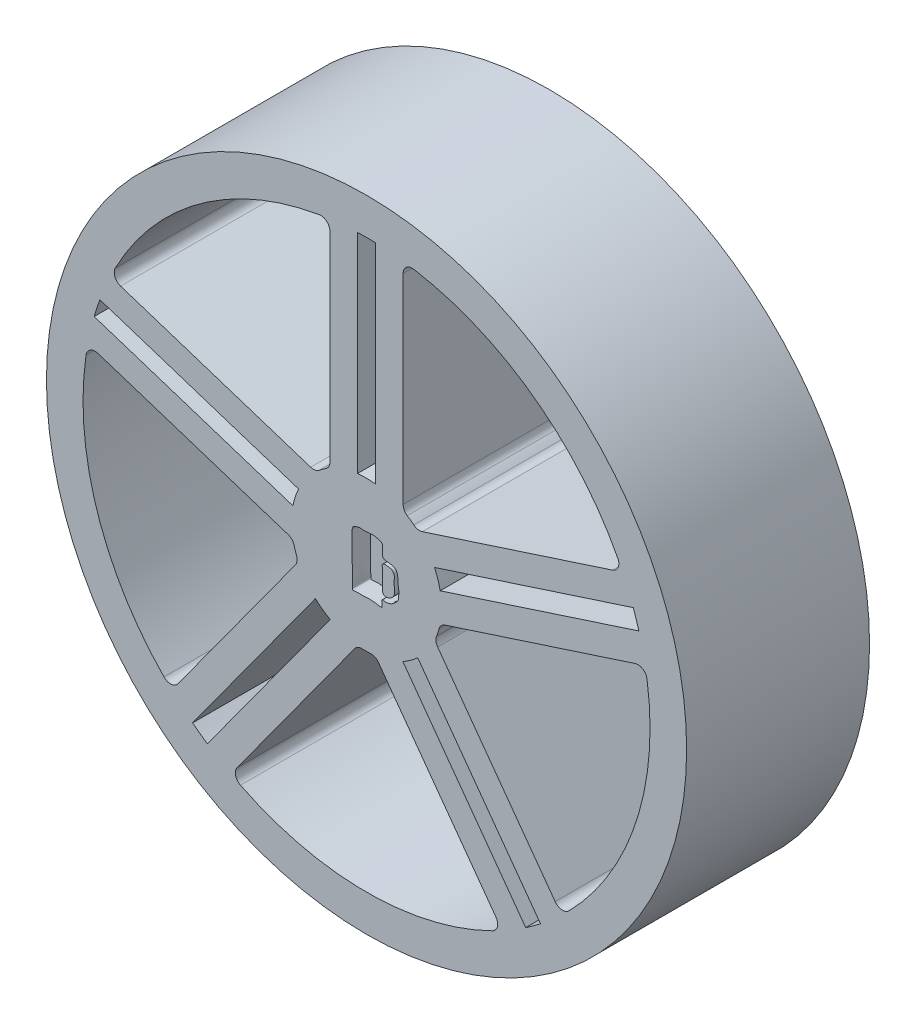
SolidWorks part; units mm, degrees
ref_plane "Plan de face" through (0, 0, 0) normal (0, 0, 1) x (1, 0, 0)
ref_plane "Plan de dessus" through (0, 0, 0) normal (0, 1, 0) x (1, 0, 0)
ref_plane "Plan de droite" through (0, 0, 0) normal (1, 0, 0) x (0, 0, -1)
sketch "Esquisse1" plane through (0, 0, 0) normal (0, 0, 1) x (1, 0, 0)
  circle A1 centre (0, 0) radius 2.1
  circle A2 centre (0, 0) radius 4.1
  dimension "D1" = 4.2
  dimension "D2" = 8.2
  dimension "D3" = 2
extrude "Boss.-Extru.1" add sketch "Esquisse1" along normal blind 6
sketch "Esquisse2" plane through (0, 0, 6) normal (0, 0, 1) x (1, 0, 0)
  line L0 (0, 0) -> (0, 4.1)
  line L1 (0, 4.1) -> (0, 3.4754)
  line L2 (0, 3.4754) -> (2, 3.4754)
  line L3 (2, 3.4754) -> (0, 3.4754)
  line L4 (0, 3.4754) -> (-2, 3.4754)
  line L6 (-2, 3.4754) -> (2, 3.4754)
  line L7 (-2, 3.4754) -> (-2, 16)
  line L8 (-2, 16) -> (2, 16)
  line L9 (2, 3.4754) -> (2, 16)
  line L10 (0, 3.4754) -> (0.5, 3.4754)
  line L11 (0, 3.4754) -> (0, 16)
  line L12 (0, 16) -> (0.5, 16)
  line L13 (0.5, 3.4754) -> (0.5, 16)
  line L14 (0, 16) -> (-0.5, 16)
  line L15 (0, 16) -> (0, 3.4754)
  line L16 (0, 3.4754) -> (-0.5, 3.4754)
  line L17 (-0.5, 16) -> (-0.5, 3.4754)
  circle A0 centre (0, 0) radius 4.1
  circle A1 centre (0, 0) radius 17.5
  circle A2 centre (0, 0) radius 15.5
  spline S0 degree 1 poles (-2, 4.9542) (-2, 16) knots 0 0 1 1
  dimension "D5" = 35
  dimension "D6" = 2
  dimension "D1" = 2
  dimension "D2" = 2
  dimension "D3" = 4
  dimension "D4" = 16
  dimension "D7" = 0.5
  dimension "D8" = 0.5
extrude "Boss.-Extru.3" add sketch "Esquisse2" along normal blind 10
fillet "Congé5" radius 0.5 4 edges at (2, 15.3704, 11) (-2, 15.3704, 11) (-2, 3.5791, 11) (2, 3.5791, 11)
pattern_circular "Répétition circulaire2" count 5 over 360 about axis through (0, 0, 0) along (0, 0, 1) of "Boss.-Extru.3"
fillet "Congé6" radius 0.5 16 edges at (-2.7859, 3.0081, 11) (-14.0001, 6.6518, 11) (-15.2362, 2.8476, 11) (-10.6525, -11.2594, 11) (-3.7218, -1.72, 11) (-4.022, -0.7961, 11) (-7.4165, -13.6105, 11) (-0.4857, -4.0711, 11) (0.4857, -4.0711, 11) (7.4165, -13.6105, 11) (10.6525, -11.2594, 11) (4.022, -0.7961, 11) (3.7218, -1.72, 11) (15.2362, 2.8476, 11) (14.0001, 6.6518, 11) (2.7859, 3.0081, 11)
sketch "Esquisse3" plane through (0, 0, 16) normal (0, 0, 1) x (1, 0, 0)
  line L0 (104.2479, 238.2551) -> (530.9145, 238.2551) construction
  spline S0 degree 3 poles (-0.726, 1.4912) (-0.819, 1.2108) (-0.7792, 0.8729) (-0.7891, 0.4359) (-0.7797, 0.004) (-0.7796, -0.4368) (-0.7907, -0.9181) (-0.7539, -1.2542) (-0.813, -1.6196) (-0.4685, -1.5267) (-0.2103, -1.5787) (0.2066, -1.5215) (0.4839, -1.5607) (0.8943, -1.6346) (0.8204, -1.4455) (0.844, -1.3437) (0.8132, -1.2285) (0.9361, -1.2012) (1.0493, -1.2644) (1.1965, -1.2144) (1.3541, -1.1889) (1.4823, -1.0709) (1.6307, -0.9669) (1.7561, -0.798) (1.7476, -0.6007) (1.7935, -0.3673) (1.7053, -0.1109) (1.7345, 0.1335) (1.699, 0.3172) (1.6753, 0.4687) (1.5677, 0.6183) (1.3504, 0.6868) (1.1436, 0.7205) (0.9429, 0.7267) (0.851, 0.89) (0.8925, 1.0428) (0.8613, 1.2198) (0.9128, 1.3787) (0.7927, 1.4916) (0.6389, 1.5312) (0.4406, 1.602) (0.2086, 1.5751) (-0.0026, 1.5642) (-0.1936, 1.538) (-0.3731, 1.5924) (-0.5398, 1.521) (-0.726, 1.4912) (-0.819, 1.2108) (-0.7792, 0.8729) knots -0.048854 -0.035486 -0.016133 0 0.041402 0.082968 0.124832 0.165418 0.21027 0.259846 0.271899 0.299275 0.326038 0.357721 0.410942 0.427867 0.442663 0.451603 0.460543 0.470438 0.478266 0.497739 0.510942 0.523849 0.546138 0.563929 0.580744 0.601196 0.631542 0.655673 0.670758 0.685175 0.699287 0.721043 0.747328 0.762106 0.773799 0.795129 0.805353 0.825589 0.836673 0.847964 0.871315 0.896056 0.913792 0.932301 0.951146 0.964514 0.983867 1 1.041402 1.082968 1.124832 only from (-0.7812, 1.304) to (-0.7812, 1.304)
  spline S1 degree 3 poles (0.8395, 0.4656) (0.8809, 0.2493) (0.8518, 0.0154) (0.8708, -0.2939) (0.8944, -0.5537) (0.8563, -0.7753) (0.9172, -1.0022) (1.1571, -0.9961) (1.3243, -0.917) (1.4716, -0.796) (1.5314, -0.6065) (1.5396, -0.3939) (1.5038, -0.1914) (1.4962, 0.0004) (1.558, 0.2179) (1.434, 0.4728) (1.1763, 0.5058) (1.0122, 0.5451) (0.8395, 0.4656) (0.8809, 0.2493) (0.8518, 0.0154) knots -0.131408 -0.062135 -0.038325 0 0.083464 0.15784 0.239391 0.285079 0.338279 0.392619 0.44152 0.487125 0.535865 0.591595 0.652937 0.696802 0.739974 0.83015 0.868592 0.937865 0.961675 1 1.083464 1.15784 1.239391 only from (0.8629, 0.3199) to (0.8629, 0.3199)
  point P8 (0.9573, 0.5411)
  point P12 (0, 0)
  point P16 (0.9603, 0.5119)
  point P20 (1.2135, 0.5027)
  point P24 (1.5013, 0)
  point P28 (1.5229, 0.1639)
  point P32 (1.5023, -0.168)
  point P36 (1.5284, -0.4015)
  point P40 (1.517, -0.6147)
  point P44 (1.4508, -0.7893)
  point P48 (1.3219, -0.9072)
  point P52 (1.1537, -0.9818)
  point P56 (0.9467, -0.9605)
  point P60 (0.8707, -0.7714)
  point P64 (0.8814, -0.5967)
  point P68 (0.8716, -0.2845)
  point P72 (0.8629, 0.3199)
  point P74 (1.2172, -1.2145)
  point P76 (1.3497, -1.1762)
  point P78 (1.6359, -0.9456)
  point P80 (1.7367, -0.7895)
  point P82 (1.7715, -0.4017)
  point P84 (1.725, -0.0881)
  point P86 (1.0971, 0.7196)
  point P88 (0.952, 0.7542)
extrude "Enlèv. mat.-Extru.1" cut sketch "Esquisse3" against normal blind 1
